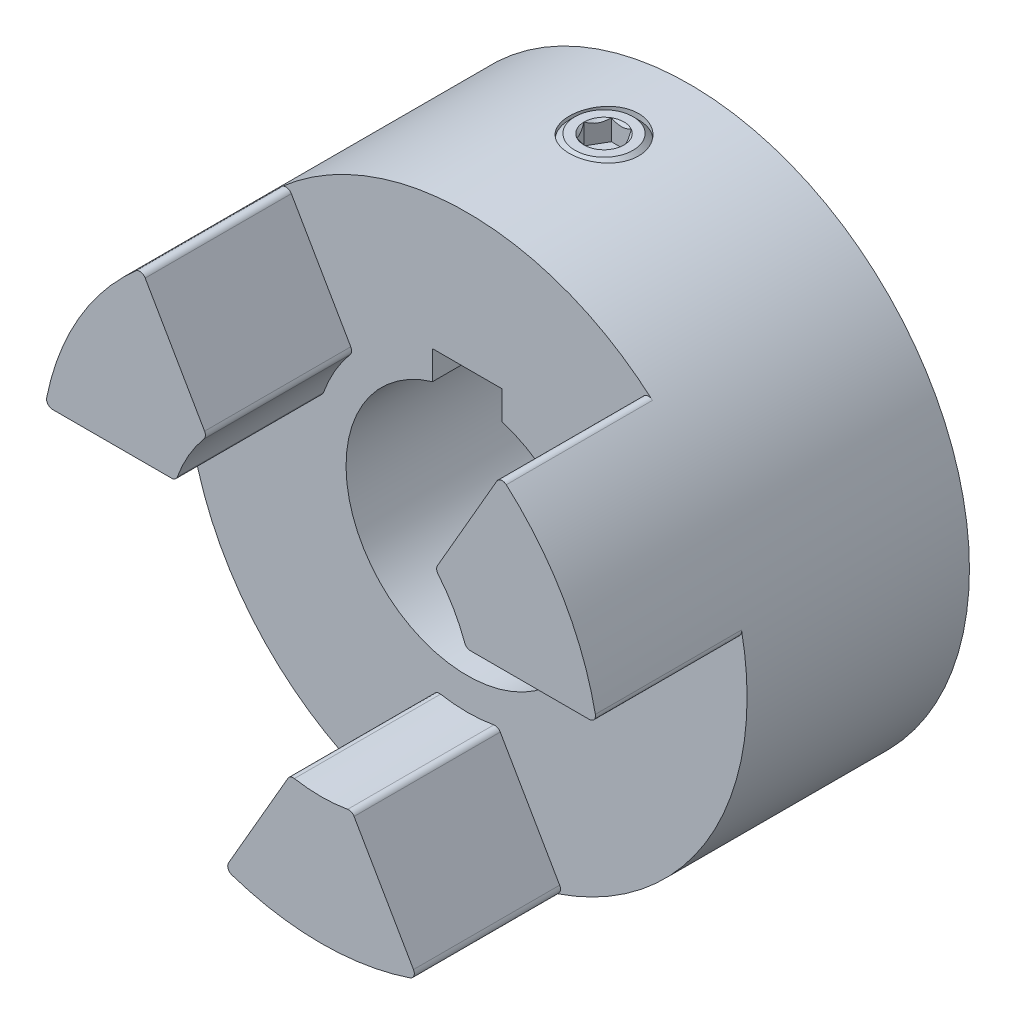
SolidWorks part; units mm, degrees
ref_plane "Front" through (0, 0, 0) normal (0, 0, 1) x (1, 0, 0)
ref_plane "Top" through (0, 0, 0) normal (0, 1, 0) x (1, 0, 0)
ref_plane "Right" through (0, 0, 0) normal (1, 0, 0) x (0, 0, -1)
sketch "Sketch3" plane through (0, 0, 0) normal (1, 0, 0) x (0, 0, -1)
  line L0 (36.1156, 0) -> (-36.1156, 0) construction
  circle A0 centre (0, 0) radius 7.7629 construction
  circle A1 centre (0, 0) radius 14 construction
  circle A2 centre (0, 0) radius 32.3453 construction
  point P7 (0, 7.7629)
  point P8 (0, -7.7629)
  point P9 (0, 14)
  point P10 (0, -14)
  point P11 (0, 32.3453)
  point P12 (0, -32.3453)
  point P13 (9.1281, 0)
  point P14 (-7.7629, 0)
  point P15 (7.7629, 0)
  point P16 (-7.7629, 32.3453)
  point P17 (36.1156, 32.3453)
  point P18 (9.1281, 32.3453)
  dimension "OD" = 64.6906
  dimension "Shaft Dia" = 28
  dimension "Overall Lg" = 72.2313
  dimension "Bore Depth" = 26.9875
  dimension "Lug Lg" = 16.891
sketch "Sketch1" plane through (0, 0, 0) normal (0, 0, 1) x (1, 0, 0)
  circle A0 centre (0, 0) radius 32.3453
  circle A1 centre (0, 0) radius 14 construction
extrude "Boss-Extrude1" add sketch "Sketch1" against normal up to vertex (36.1156 mm away) from vertex up to point (0, 0, -36.1156) starting at point (0, 0, -9.1281)
sketch "Sketch10" [suppressed] plane through (0, 0, -3.5719) normal (0, 0, 1) x (1, 0, 0)
  arc A14 (-1.0963, -4.1108) -> (1.0963, -4.1108) centre (0, 0) ccw
  arc A15 (-3.4409, -7.1529) -> (-1.0963, -4.1108) centre (-9.5758, 0) ccw
  arc A19 (1.0963, -4.1108) -> (3.4409, -7.1529) centre (9.5758, 0) ccw
  circle A32 centre (0, 0) radius 7.9375 construction
  arc A33 (-3.4409, -7.1529) -> (3.4409, -7.1529) centre (0, 0) ccw
  point P0 (0, -4.2545)
  point P1 (0, -7.9375)
  dimension "D1" = 3.683
  dimension "D4" = 9.4234
  dimension "D2" = 6.8819
  dimension "D3" = 2.1926
extrude "Boss-Extrude4" [suppressed] add sketch "Sketch10" along normal up to vertex up to point (0, 0, 7.7629)
fillet "Fillet2" [suppressed] radius 0.381
other "Move Face3" [suppressed] parameters "D1"=90
pattern_circular "CirPattern2" [suppressed] count 2 over 360 of bodies 116
sketch "Sketch11" [suppressed] plane through (0, 0, -5.9531) normal (0, 0, 1) x (1, 0, 0)
  arc A0 (-1.5825, -7.8835) -> (1.5738, -7.8835) centre (-0.0044, -0.0397) ccw
  arc A1 (-1.5825, -7.8835) -> (-2.9616, -8.354) centre (-1.8681, -9.3029) ccw
  arc A2 (-2.9616, -8.354) -> (-4.9794, -11.8231) centre (5.1535, -15.3956) ccw
  arc A3 (-4.9794, -11.8231) -> (-4.4308, -12.9555) centre (-4.1442, -12.1175) ccw
  arc A4 (-4.4308, -12.9555) -> (4.4176, -12.96) centre (0, 0) ccw
  arc A5 (4.4176, -12.96) -> (4.9692, -11.8231) centre (4.1308, -12.1185) ccw
  arc A6 (4.9692, -11.8231) -> (2.9523, -8.354) centre (-5.1643, -15.3938) ccw
  arc A7 (2.9523, -8.354) -> (1.5738, -7.8835) centre (1.8592, -9.3021) ccw
  circle A8 centre (0, 0) radius 13.6922 construction
  point P18 (-0.007, -13.6922)
  point P19 (-0.0044, -8.0407)
  dimension "D1" = 1.4478
  dimension "D2" = 8.001
  dimension "D3" = 10.7442
  dimension "D4" = 0.889
  dimension "D9" = 5.6515
  dimension "D5" = 5.072
  dimension "D6" = 3.1563
  dimension "D7" = 5.9139
  dimension "D8" = 9.9486
extrude "Boss-Extrude5" [suppressed] add sketch "Sketch11" along normal up to vertex up to point (0, 0, 7.7629)
other "Move Face1" [suppressed] parameters "D1"=90
pattern_circular "CirPattern3" [suppressed] count 2 over 360 of bodies 118
sketch "Sketch12" [suppressed] plane through (0, 0, -6.1516) normal (0, 0, 1) x (1, 0, 0)
  line L0 (-5.1097, -10.267) -> (-8.533, -13.6894)
  line L1 (8.533, -13.6894) -> (5.1097, -10.267)
  arc A0 (-2.3442, -9.4968) -> (2.3442, -9.4968) centre (0, 0) ccw
  arc A1 (-2.3442, -9.4968) -> (-5.1097, -10.267) centre (-3.0443, -12.333) ccw
  arc A2 (-8.533, -13.6894) -> (-8.3299, -15.1215) centre (-7.8934, -14.3292) ccw
  arc A3 (-8.3299, -15.1215) -> (8.3299, -15.1215) centre (0, 0) ccw
  arc A4 (8.3299, -15.1215) -> (8.533, -13.6894) centre (7.8934, -14.3292) ccw
  arc A5 (5.1097, -10.267) -> (2.3442, -9.4968) centre (3.0443, -12.333) ccw
  circle A6 centre (0, 0) radius 17.2641 construction
  point P16 (0, -9.7819)
  point P17 (0, -17.2641)
  dimension "D1" = 7.4822
  dimension "D2" = 10.2193
  dimension "D3" = 4.6884
  dimension "D4" = 17.066
  dimension "D5" = 16.6598
extrude "Boss-Extrude6" [suppressed] add sketch "Sketch12" along normal up to vertex up to point (0, 0, 7.7629)
other "Move Face2" [suppressed] parameters "D1"=90
pattern_circular "CirPattern4" [suppressed] count 2 over 360 of bodies 120
sketch "Sketch2" plane through (0, 0, -9.1281) normal (0, 0, 1) x (1, 0, 0)
  line L0 (-11.1144, -30.3758) -> (-3.5662, -17.302)
  line L2 (3.5662, -17.302) -> (11.1144, -30.3758)
  circle A0 centre (0, 0) radius 32.3453 construction
  arc A1 (-11.1144, -30.3758) -> (11.1144, -30.3758) centre (0, 0) ccw
  arc A2 (-3.5662, -17.302) -> (3.5662, -17.302) centre (0, 0) ccw
  circle A3 centre (0, 0) radius 5.5626 construction
  dimension "Spider Inner body Dia" = 35.3314
  dimension "Spider Leg Thickness" = 11.1252
  dimension "D4" = 7.1324
  dimension "D1" = 60
extrude "Boss-Extrude2" add sketch "Sketch2" along normal up to vertex (16.891 mm away) up to point (0, 0, 7.7629)
fillet "Fillet1" radius 0.7132 4 edges at (3.5662, -17.302, -0.6826) (-3.5662, -17.302, -0.6826)
pattern_circular "CirPattern1" count 3 over 360 about axis through (0, 0, -36.1156) along (0, 0, 1) of "Boss-Extrude2", "Fillet1"
sketch "Sketch15" plane through (0, 0, 0) normal (0, 0, 1) x (1, 0, 0)
  circle A0 centre (0, 0) radius 14
extrude "Cut-Extrude5" cut sketch "Sketch15" against normal through all and the other way through all
chamfer "Chamfer1" distance 1.2938 angle 56 2 edges at (32.3453, 0, -36.1156) (14, 0, -36.1156) first distance on face at (32.3453, 0, -36.1156) first distance on face at (14, 0, -9.1281)
sketch "Sketch4" plane through (0, 0, 0) normal (0, 0, 1) x (1, 0, 0)
  line L1 (-4, 16.7164) -> (4, 16.7164)
  line L2 (-4, 16.7164) -> (-4, 13.4164)
  line L4 (4, 16.7164) -> (4, 13.4164)
  arc A1 (4, 13.4164) -> (-4, 13.4164) centre (0, 0) ccw
  circle A2 centre (0, 0) radius 14 construction
  dimension "Keyway Ht" = 3.3
  dimension "Keyway Wd" = 8
extrude "Cut-Extrude1" cut sketch "Sketch4" against normal through all and the other way through all
sketch "Sketch5" plane through (0, 0, 0) normal (0, 1, 0) x (1, 0, 0)
  line L1 (0, -46.4939) -> (0, 46.4939) construction
  circle A0 centre (0, 24.9396) radius 4
  dimension "Screw Dia" = 8
  dimension "Screw Offset" = 11.176
extrude "Cut-Extrude2" cut sketch "Sketch5" along normal through all
ref_plane "Plane1" through (0, 32.3453, 0) normal (0, 1, 0) x (-1, 0, 0)
sketch "Sketch6" plane through (0, 32.3453, 0) normal (0, 1, 0) x (-1, 0, 0)
  circle A1 centre (0, -24.9396) radius 4
  circle A2 centre (0, -24.9396) radius 4
  dimension "D1" = 0
extrude "Boss-Extrude3" add sketch "Sketch6" against normal blind 12 separate body
sketch "Sketch8" plane through (0, 32.3453, 0) normal (0, 1, 0) x (1, 0, 0)
  line L1 (1.1547, 22.9396) -> (2.3094, 24.9396)
  line L2 (2.3094, 24.9396) -> (1.1547, 26.9396)
  line L3 (1.1547, 26.9396) -> (-1.1547, 26.9396)
  line L4 (-1.1547, 26.9396) -> (-2.3094, 24.9396)
  line L5 (-2.3094, 24.9396) -> (-1.1547, 22.9396)
  line L6 (-1.1547, 22.9396) -> (1.1547, 22.9396)
  circle A0 centre (0, 24.9396) radius 2 construction
  dimension "D1" = 4
extrude "Cut-Extrude3" cut sketch "Sketch8" against normal blind 2.4
sketch "Sketch9" plane through (0, 32.3453, 0) normal (0, 1, 0) x (1, 0, 0)
  circle A0 centre (0, 24.9396) radius 2.3094
extrude "Cut-Extrude4" cut sketch "Sketch9" against normal through all draft 45
chamfer "Chamfer3" distance 0.64 angle 45 1 edges at (0, 32.3453, -20.9396)
chamfer "Chamfer4" distance 1.36 angle 45 1 edges at (0, 20.3453, -20.9396)
sketch "Sketch16" [suppressed] plane through (0, 0, -61.9125) normal (0, 0, -1) x (-1, 0, 0)
  circle A0 centre (0, 0) radius 50.8
  dimension "D1" = 101.6
extrude "Cut-Extrude6" [suppressed] cut sketch "Sketch16" against normal blind 30.3022 flip side to cut
chamfer "Chamfer5" [suppressed] distance 1.778 angle 56
fillet "Fillet3" [suppressed] radius 1.27
move or copy body "Body-Move/Copy1" [suppressed] bodies to move or copy 115 copy no translate (0, -6.35, 0)
sketch "Sketch17" [suppressed] plane through (0, 0, -67.8656) normal (0, 0, -1) x (-1, 0, 0)
  circle A0 centre (0, 0) radius 53.975
  dimension "D1" = 107.95
extrude "Cut-Extrude7" [suppressed] cut sketch "Sketch17" against normal blind 36.576 flip side to cut
move or copy body "Body-Move/Copy2" [suppressed] bodies to move or copy 115 copy no translate (0, -9.525, 0)
fillet "Fillet4" [suppressed] radius 2.54
fillet "Fillet5" [suppressed] radius 1.27
equation "\"D1@Chamfer1\" = \"OD@Sketch3\" * .02"
equation "\"D1@Fillet1\" = \"D4@Sketch2\" * .1"
equation "\"D1@Sketch8\" = \"Screw Dia@Sketch5\" * .5"
equation "\"D1@Cut-Extrude3\" = \"Screw Dia@Sketch5\" * .3"
equation "\"D1@Chamfer3\" = \"Screw Dia@Sketch5\" * .08"
equation "\"D1@Chamfer4\" = \"Screw Dia@Sketch5\" * .17"
